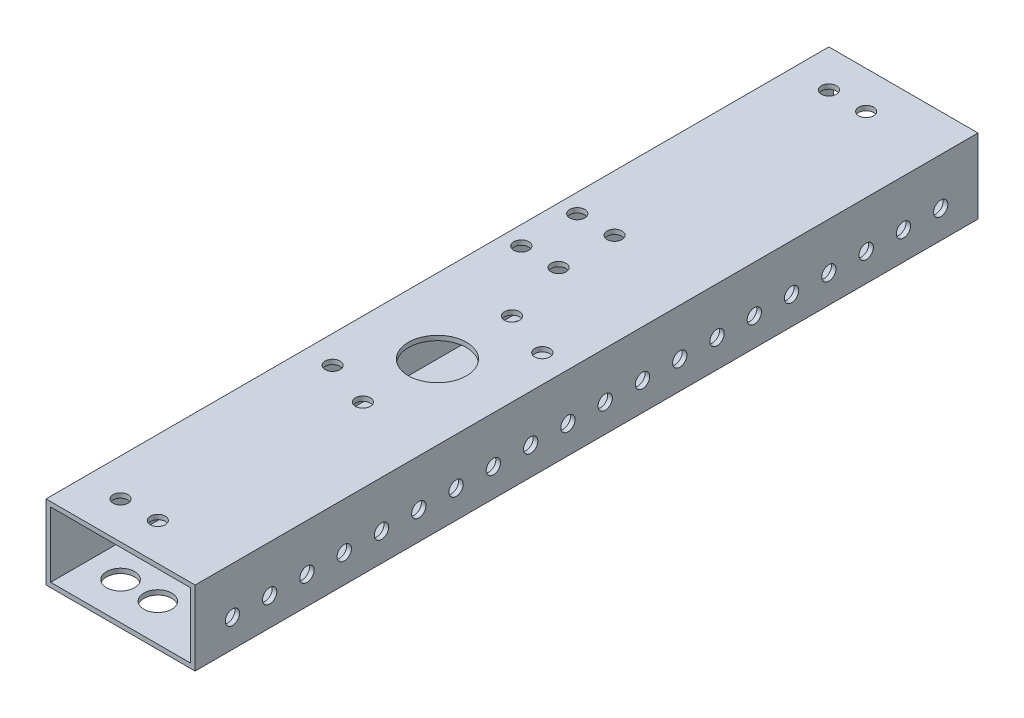
SolidWorks part; units mm, degrees
other "Markup1"
sketch "Sketch7" plane through (25.4, 12.7, -127) normal (0.9965, 0.0171, -0.0817) x (-0.082, 0.0128, -0.9966)
sketch "Sketch8" plane through (25.4, 12.7, -127) normal (0.9965, 0.0171, -0.0817) x (-0.082, 0.0128, -0.9966)
sketch "Sketch9" plane through (25.4, 12.7, -127) normal (0.9965, 0.0171, -0.0817) x (-0.082, 0.0128, -0.9966)
sketch "Sketch12" plane through (25.4, 12.7, -127) normal (0.9965, 0.0171, -0.0817) x (-0.082, 0.0128, -0.9966)
sketch "Sketch13" plane through (25.4, 12.7, -127) normal (0.9965, 0.0171, -0.0817) x (-0.082, 0.0128, -0.9966)
sketch "Sketch14" plane through (25.4, 12.7, -127) normal (0.9965, 0.0171, -0.0817) x (-0.082, 0.0128, -0.9966)
sketch "Sketch15" plane through (25.4, 12.7, -133.35) normal (0.9965, 0.0171, -0.0817) x (-0.082, 0.0128, -0.9966)
material "6061-T6 (SS)"
ref_plane "Front Plane" through (0, 0, 0) normal (0, 0, 1) x (1, 0, 0)
ref_plane "Top Plane" through (0, 0, 0) normal (0, 1, 0) x (1, 0, 0)
ref_plane "Right Plane" through (0, 0, 0) normal (1, 0, 0) x (0, 0, -1)
sketch "Sketch1" plane through (0, 0, 0) normal (0, 0, 1) x (1, 0, 0)
  line L0 (-23.8125, 11.1125) -> (23.8125, 11.1125)
  line L1 (-25.4, -12.7) -> (25.4, -12.7)
  line L2 (-25.4, -12.7) -> (-25.4, 12.7)
  line L3 (-25.4, 12.7) -> (25.4, 12.7)
  line L4 (25.4, -12.7) -> (25.4, 12.7)
  line L5 (-25.4, -12.7) -> (25.4, 12.7) construction
  line L6 (-25.4, 12.7) -> (25.4, -12.7) construction
  line L7 (23.8125, -11.1125) -> (23.8125, 11.1125)
  line L8 (-23.8125, -11.1125) -> (23.8125, -11.1125)
  line L9 (-23.8125, -11.1125) -> (-23.8125, 11.1125)
  point P0 (0, 0)
  dimension "D1" = 50.8
  dimension "D2" = 25.4
  dimension "D3" = 1.5875
extrude "Boss-Extrude1" add sketch "Sketch1" along normal mid plane 266.7
sketch "Sketch3" plane through (0, 12.7, 0) normal (0, 1, 0) x (1, 0, 0)
  line L0 (25.4, 133.35) -> (-25.4, 133.35) construction
  line L1 (25.4, -133.35) -> (-25.4, -133.35) construction
  line L3 (-25.4, -133.35) -> (-25.4, 133.35) construction
  line L4 (25.4, -133.35) -> (25.4, 133.35) construction
  circle A0 centre (-12.7, -120.65) radius 2.5527
  circle A1 centre (0, -120.65) radius 2.5527
  circle A2 centre (-12.7, 120.65) radius 2.5527
  circle A3 centre (0, 120.65) radius 2.5527
  dimension "D5" = 5.1054
  dimension "D1" = 12.7
  dimension "D2" = 12.7
  dimension "D3" = 12.7
  dimension "D4" = 12.7
  dimension "D6" = 12.7
  dimension "D7" = 12.7
  dimension "D8" = 12.7
  dimension "D9" = 25.4
  dimension "D10" = 12.7
  dimension "D11" = 25.4
extrude "Cut-Extrude1" cut sketch "Sketch3" against normal up to surface (1.5875 mm away) up to face at (0, 11.1125, 0)
sketch "Sketch5" plane through (0, -12.7, 0) normal (0, -1, 0) x (1, 0, 0)
  circle A0 centre (-12.7, -120.65) radius 2.5527 construction
  circle A1 centre (0, -120.65) radius 2.5527 construction
  circle A2 centre (0, 120.65) radius 2.5527 construction
  circle A3 centre (-12.7, 120.65) radius 2.5527 construction
  circle A4 centre (-12.7, -120.65) radius 2.5527
  circle A5 centre (0, -120.65) radius 2.5527
  circle A6 centre (0, 120.65) radius 2.5527
  circle A7 centre (-12.7, 120.65) radius 2.5527
  circle A8 centre (-12.7, 120.65) radius 4.7625
  circle A9 centre (0, 120.65) radius 4.7625
  circle A10 centre (0, -120.65) radius 4.7625
  circle A11 centre (-12.7, -120.65) radius 4.7625
  dimension "D1" = 9.525
extrude "Cut-Extrude2" cut sketch "Sketch5" against normal up to surface (1.5875 mm away) contours A10 A5 | A5 | A11 A4 | A4 | A6 | A9 A6 | A8 A7 | A7 region at (-12.7, -12.7, -120.65) region at (0, -12.7, -120.65) region at (0, -12.7, 120.65) region at (-12.7, -12.7, 120.65) region at (-17.3278, -12.7, 120.65) region at (-4.6278, -12.7, 120.65) region at (-4.6278, -12.7, -120.65) region at (-17.3278, -12.7, -120.65) up to face at (0, -11.1125, 0)
sketch "Sketch6" plane through (25.4, 0, 0) normal (1, 0, 0) x (0, 0, -1)
  line L0 (-133.35, -12.7) -> (-133.35, 12.7) construction
  line L1 (-133.35, -12.7) -> (133.35, -12.7) construction
  line L2 (0, 12.7) -> (0, -12.7) construction
  line L3 (-133.35, 12.7) -> (133.35, 12.7) construction
  circle A0 centre (-120.65, -3.175) radius 2.4384
  circle A19 centre (-107.95, -3.175) radius 2.4384
  circle A20 centre (-95.25, -3.175) radius 2.4384
  circle A21 centre (-82.55, -3.175) radius 2.4384
  circle A22 centre (-69.85, -3.175) radius 2.4384
  circle A23 centre (-57.15, -3.175) radius 2.4384
  circle A24 centre (-44.45, -3.175) radius 2.4384
  circle A25 centre (-31.75, -3.175) radius 2.4384
  circle A26 centre (-19.05, -3.175) radius 2.4384
  circle A27 centre (-6.35, -3.175) radius 2.4384
  circle A28 centre (6.35, -3.175) radius 2.4384
  circle A29 centre (19.05, -3.175) radius 2.4384
  circle A30 centre (31.75, -3.175) radius 2.4384
  circle A31 centre (44.45, -3.175) radius 2.4384
  circle A32 centre (57.15, -3.175) radius 2.4384
  circle A33 centre (69.85, -3.175) radius 2.4384
  circle A34 centre (82.55, -3.175) radius 2.4384
  circle A35 centre (95.25, -3.175) radius 2.4384
  circle A36 centre (107.95, -3.175) radius 2.4384
  circle A37 centre (120.65, -3.175) radius 2.4384
  dimension "D1" = 4.8768
  dimension "D5" = 12.7
  dimension "D2" = 12.7
  dimension "D3" = 9.525
  dimension "D4" = 20
extrude "Cut-Extrude3" cut sketch "Sketch6" against normal up to next contours A0 | A19 | A20 | A21 | A23 | A22 | A24 | A25 | A26 | A27 | A28 | A29 | A30 | A31 | A32 | A37 | A36 | A35 | A34 | A33 | A24 | A33 region at (25.4, -3.175, 120.65) region at (25.4, -3.175, 107.95) region at (25.4, -3.175, 95.25) region at (25.4, -3.175, 82.55) region at (25.4, -3.175, 69.85) region at (25.4, -3.175, 57.15) region at (25.4, -3.175, 44.45) region at (25.4, -3.175, 31.75) region at (25.4, -3.175, 19.05) region at (25.4, -3.175, 6.35) region at (25.4, -3.175, -6.35) region at (25.4, -3.175, -19.05) region at (25.4, -3.175, -31.75) region at (25.4, -3.175, -44.45) region at (25.4, -3.175, -57.15) region at (25.4, -3.175, -69.85) region at (25.4, -3.175, -82.55) region at (25.4, -3.175, -95.25) region at (25.4, -3.175, -107.95) region at (25.4, -3.175, -120.65)
sketch "Sketch11" plane through (0, 12.7, 0) normal (0, 1, 0) x (1, 0, 0)
  line L0 (-25.4, -133.35) -> (-25.4, 133.35) construction
  line L1 (-6.35, 41.275) -> (-6.35, 22.225) construction
  line L2 (0, 0) -> (0, -50.8) construction
  line L3 (25.4, 133.35) -> (-25.4, 133.35) construction
  line L5 (-19.05, 41.275) -> (-3.7973, 41.275) construction
  line L6 (-19.05, 41.275) -> (-19.05, 22.225) construction
  line L7 (-19.05, 22.225) -> (-3.7973, 22.225) construction
  line L9 (-19.05, 41.275) -> (-16.8611, 39.9616) construction
  line L10 (-19.05, 22.225) -> (-16.8611, 23.5384) construction
  line L13 (-19.05, -34.925) -> (-19.05, -15.875) construction
  line L14 (-15.9944, -45.1317) -> (15.9944, -5.6683) construction
  circle A0 centre (0, -25.4) radius 9.906
  circle A1 centre (0, 0) radius 2.5527
  circle A2 centre (0, -50.8) radius 2.5527
  circle A4 centre (-19.05, 22.225) radius 2.5527
  circle A5 centre (-19.05, 41.275) radius 2.5527
  circle A7 centre (-6.35, 22.225) radius 2.5527
  circle A8 centre (-6.35, 41.275) radius 2.5527
  circle A13 centre (15.9944, -5.6683) radius 2.5527
  circle A14 centre (-15.9944, -45.1317) radius 2.5527
  point P2 (0, -25.4)
  point P8 (-3.175, 31.75)
  point P9 (12.1427, -3.0905)
  point P24 (0, -25.4)
  point P28 (-8.9948, -8.8622)
  dimension "D1" = 19.812
  dimension "D3" = 5.1054
  dimension "D4" = 25.4
  dimension "D5" = 19.05
  dimension "D6" = 5.1054
  dimension "D7" = 12.7
  dimension "D10" = 39.028
  dimension "D2" = 25.4
  dimension "D8" = 101.6
  dimension "D9" = 6.35
  dimension "D11" = 19.05
  dimension "D12" = 22.225
  dimension "1" = 25.4
extrude "Cut-Extrude4" cut sketch "Sketch11" against normal through all
